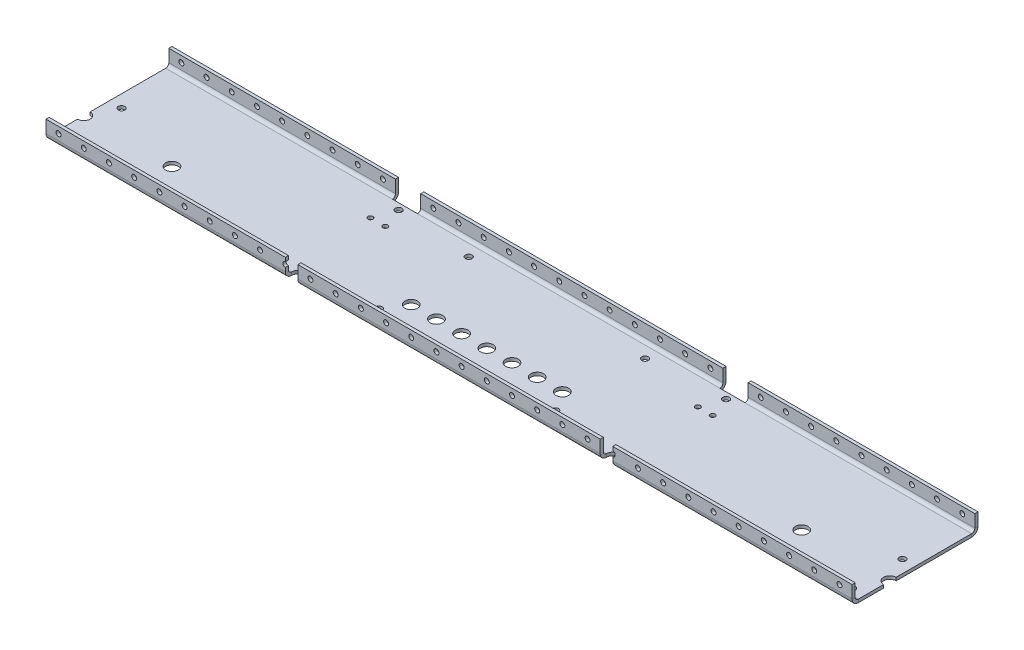
SolidWorks part; units mm, degrees
note: The reader was unsure of these and kept them because the rebuilt part matched: thickness of "Base-Flange1", "Edge-Flange1", "Sheet-Metal1", "Sheet-Metal2", "Sheet-Metal9", "Sheet-Metal10", "Sheet-Metal11", "Sheet-Metal12", "Sheet-Metal13", "Sheet-Metal14", "Sheet-Metal15", "Sheet-Metal16", "Sheet-Metal17", "Sheet-Metal18"; flange length of "Edge-Flange1".
ref_plane "Front Plane" through (0, 0, 0) normal (0, 0, 1) x (1, 0, 0)
ref_plane "Top Plane" through (0, 0, 0) normal (0, 1, 0) x (1, 0, 0)
ref_plane "Right Plane" through (0, 0, 0) normal (1, 0, 0) x (0, 0, -1)
sketch "Sketch1" plane through (0, 0, 0) normal (0, 1, 0) x (1, 0, 0)
  line L1 (406.4, -63.5) -> (-406.4, -63.5)
  line L2 (406.4, -63.5) -> (406.4, 63.5)
  line L3 (406.4, 63.5) -> (-406.4, 63.5)
  line L4 (-406.4, -63.5) -> (-406.4, 63.5)
  line L5 (406.4, -63.5) -> (-406.4, 63.5) construction
  line L6 (406.4, 63.5) -> (-406.4, -63.5) construction
  point P0 (0, 0)
  dimension "D1" = 127
  dimension "D2" = 812.8
base flange "Base-Flange1" sketch "Sketch1" thickness 3.175 reverse thickness direction no parameters "D1"=1
edge flange "Edge-Flange1" sketch "Sketch23" flange profiles "Sketch23", "Sketch25" flange angle 90 flange length 19.05 flange position material inside bend radius 3.175 thickness 3.175 relief rectangular parameters "D6"=10, "D8"=1
bend "EdgeBend1" bend radius 3.175 bend angle 90 parameters "D5"=1
bend "EdgeBend2" bend radius 3.175 bend angle 90 parameters "D5"=2
sketch "Sketch23" plane through (0, 0, -63.5) normal (0, 0, -1) x (-1, 0, 0)
  line L0 (-406.4, 0) -> (406.4, 0) construction
  line L1 (-406.4, 0) -> (406.4, 0)
  line L2 (-406.4, 0) -> (-406.4, 15.875)
  line L3 (-406.4, 15.875) -> (406.4, 15.875)
  line L4 (406.4, 15.875) -> (406.4, 0)
sketch "Sketch25" plane through (0, 0, 63.5) normal (0, 0, 1) x (1, 0, 0)
  line L0 (-406.4, 0) -> (406.4, 0) construction
  line L1 (-406.4, 0) -> (406.4, 0)
  line L2 (-406.4, 0) -> (-406.4, 15.875)
  line L3 (-406.4, 15.875) -> (406.4, 15.875)
  line L4 (406.4, 15.875) -> (406.4, 0)
hole_wizard "Mounting Holes" positions "Sketch19" profile "Sketch20" hole size "Ø5.0" standard "ANSI Metric" end condition through all
sketch "Sketch19" plane through (342.9, 0, -63.5) normal (0, 0, 1) x (1, 0, 0)
  line L0 (63.5, 9.525) -> (-749.3, 9.525) construction
  line L3 (63.5, 15.875) -> (63.5, 3.175) construction
  point P9 (-736.6, 9.525)
  dimension "D1" = 12.7
sketch "Sketch20" plane through (-393.7, 9.525, -63.5) normal (1, 0, 0) x (0, 1, 0)
  line L0 (0, 0) -> (0, 228.6)
  line L1 (0, 228.6) -> (2.5, 228.6)
  line L2 (2.5, 228.6) -> (2.5, 0)
  line L5 (2.5, 0) -> (0, 0)
  line L11 (0, -6.35) -> (0, 107.95) construction
  dimension "Thru Hole Dia." = 5
  dimension "Thru Hole Depth" = 228.6
pattern_linear "LPattern3" count 32 spacing 25.4 along (1, 0, 0) of "Mounting Holes"
sketch "Sketch21" plane through (0, -3.175, 0) normal (0, -1, 0) x (1, 0, 0)
  line L0 (406.4, 0) -> (177.8, 0) construction
  line L3 (177.8, -57.15) -> (152.4, -57.15)
  line L4 (177.8, -57.15) -> (177.8, -63.5)
  line L5 (177.8, -63.5) -> (152.4, -63.5)
  line L6 (152.4, -57.15) -> (152.4, -63.5)
  line L7 (-177.8, 0) -> (-406.4, 0) construction
  line L8 (-152.4, -63.5) -> (-177.8, -63.5)
  line L9 (-152.4, -63.5) -> (-152.4, -57.15)
  line L10 (-152.4, -57.15) -> (-177.8, -57.15)
  line L11 (-177.8, -63.5) -> (-177.8, -57.15)
  line L12 (-406.4, -57.15) -> (-406.4, 57.15) construction
  line L13 (406.4, 57.15) -> (406.4, -57.15) construction
  line L14 (-406.4, -63.5) -> (406.4, -63.5) construction
  line L15 (-406.4, -57.15) -> (406.4, -57.15) construction
  dimension "D1" = 228.6
  dimension "D3" = 25.4
extrude "Cut-Extrude3" cut sketch "Sketch21" against normal through all normal cut yes
sketch "Sketch26" plane through (0, 0, 0) normal (0, 1, 0) x (1, 0, 0)
  line L0 (406.4, -57.15) -> (-406.4, -57.15) construction
  line L1 (152.4, -57.15) -> (152.4, -63.5)
  line L2 (406.4, -63.5) -> (-406.4, -63.5) construction
  line L3 (152.4, -63.5) -> (165.1, -63.5)
  line L4 (165.1, -63.5) -> (165.1, -57.15)
  line L5 (-165.1, -57.15) -> (-165.1, -63.5)
  line L6 (-165.1, -63.5) -> (-152.4, -63.5)
  line L7 (-152.4, -63.5) -> (-152.4, -57.15)
  line L12 (0, 158.0045) -> (0, -158.0045) construction
  line L13 (152.4, -63.5) -> (-152.4, -63.5) construction
  arc A0 (-165.1, -57.15) -> (-152.4, -57.15) centre (-158.75, -57.15) cw
  arc A1 (152.4, -57.15) -> (165.1, -57.15) centre (158.75, -57.15) cw
  point P26 (0, 0)
  point P29 (0, -63.5)
  dimension "D2" = 6.35
  dimension "D1" = 304.8
extrude "Cut-Extrude4" cut sketch "Sketch26" against normal through all both and the other way through all
hole_wizard "80/20 Connection Holes" positions "Sketch27" profile "Sketch28" hole size "Ø6.0" standard "ANSI Metric" end condition through all
sketch "Sketch27" plane through (0, 0, 0) normal (0, 1, 0) x (1, 0, 0)
  line L0 (-152.4, 63.5) -> (152.4, 63.5) construction
  line L1 (-393.7, 0) -> (-393.7, -50.8) construction
  line L3 (393.7, -50.8) -> (393.7, 0) construction
  line L4 (406.4, -57.15) -> (406.4, 57.15) construction
  line L5 (393.7, -25.4) -> (406.4, -25.4) construction
  line L7 (-393.7, -25.4) -> (-406.4, -25.4) construction
  line L8 (-406.4, 57.15) -> (-406.4, -57.15) construction
  line L10 (393.7, -50.8) -> (393.7, -57.15) construction
  line L11 (406.4, -57.15) -> (165.1, -57.15) construction
  line L13 (-393.7, -50.8) -> (-393.7, -57.15) construction
  line L14 (-165.1, -57.15) -> (-406.4, -57.15) construction
  point P0 (-165.1, 50.8)
  point P2 (165.1, 50.8)
  point P10 (-393.7, 0)
  point P11 (-393.7, -50.8)
  point P14 (393.7, -50.8)
  point P15 (393.7, 0)
  dimension "D1" = 12.7
  dimension "D2" = 12.7
  dimension "D3" = 12.7
  dimension "D4" = 12.7
  dimension "D5" = 12.7
  dimension "D6" = 50.8
  dimension "D7" = 31.75
sketch "Sketch28" plane through (-165.1, 0, -50.8) normal (1, 0, 0) x (0, 0, 1)
  line L0 (0, 0) -> (0, 3.175)
  line L1 (0, 3.175) -> (3.3, 3.175)
  line L2 (3.3, 3.175) -> (3.3, 0)
  line L5 (3.3, 0) -> (0, 0)
  line L11 (0, -6.35) -> (0, 107.95) construction
  dimension "Thru Hole Dia." = 6.6
  dimension "Thru Hole Depth" = 3.175
hole_wizard "Motor Holes" positions "Sketch29" profile "Sketch30" hole size "1/2" standard "ANSI Inch" end condition through all
sketch "Sketch29" plane through (0, 0, 0) normal (0, 1, 0) x (1, 0, 0)
  line L0 (-165.1, -63.5) -> (-406.4, -63.5) construction
  line L1 (-317.5, -25.4) -> (317.5, -25.4) construction
  line L3 (0, 0) -> (0, -25.4) construction
  line L5 (-406.4, 57.15) -> (-406.4, -57.15) construction
  point P0 (-317.5, -25.4)
  point P2 (317.5, -25.4)
  dimension "D1" = 38.1
  dimension "D2" = 88.9
sketch "Sketch30" plane through (-317.5, 0, 25.4) normal (1, 0, 0) x (0, 0, 1)
  line L0 (0, 0) -> (0, 3.175)
  line L1 (0, 3.175) -> (6.35, 3.175)
  line L2 (6.35, 3.175) -> (6.35, 0)
  line L5 (6.35, 0) -> (0, 0)
  line L11 (0, -6.35) -> (0, 107.95) construction
  dimension "Thru Hole Dia." = 12.7
  dimension "Thru Hole Depth" = 3.175
hole_wizard "1/2 (0.5) Diameter Hole1" positions "Sketch31" profile "Sketch32" hole size "1/2" standard "ANSI Inch" end condition through all
sketch "Sketch31" plane through (0, 0, 0) normal (0, 1, 0) x (1, 0, 0)
  line L0 (0, 0) -> (0, -25.4) construction
  line L2 (0, -25.4) -> (-25.4, -25.4) construction
  line L3 (-25.4, -25.4) -> (-50.8, -25.4) construction
  line L4 (-50.8, -25.4) -> (-76.2, -25.4) construction
  line L6 (0, -25.4) -> (25.4, -25.4) construction
  line L7 (25.4, -25.4) -> (50.8, -25.4) construction
  line L8 (50.8, -25.4) -> (76.2, -25.4) construction
  line L9 (152.4, -63.5) -> (-152.4, -63.5) construction
  point P2 (0, -25.4)
  point P8 (-25.4, -25.4)
  point P10 (-50.8, -25.4)
  point P12 (-76.2, -25.4)
  point P17 (25.4, -25.4)
  point P19 (50.8, -25.4)
  point P21 (76.2, -25.4)
  dimension "D1" = 25.4
  dimension "D2" = 38.1
sketch "Sketch32" plane through (76.2, 0, 25.4) normal (1, 0, 0) x (0, 0, 1)
  line L0 (0, 0) -> (0, 3.175)
  line L1 (0, 3.175) -> (6.35, 3.175)
  line L2 (6.35, 3.175) -> (6.35, 0)
  line L5 (6.35, 0) -> (0, 0)
  line L11 (0, -6.35) -> (0, 107.95) construction
  dimension "Thru Hole Dia." = 12.7
  dimension "Thru Hole Depth" = 3.175
sketch "Sketch33" plane through (0, 0, 0) normal (0, 1, 0) x (1, 0, 0)
  line L0 (-406.4, -63.5) -> (-406.4, -25.4) construction
  line L1 (-406.4, 57.15) -> (-406.4, -57.15) construction
  line L2 (-406.4, -19.05) -> (-406.4, -31.75)
  line L3 (406.4, -63.5) -> (406.4, -25.4) construction
  line L4 (406.4, -57.15) -> (406.4, 57.15) construction
  line L5 (406.4, -19.05) -> (406.4, -31.75)
  arc A0 (-406.4, -19.05) -> (-406.4, -31.75) centre (-406.4, -25.4) cw
  arc A1 (406.4, -19.05) -> (406.4, -31.75) centre (406.4, -25.4) ccw
  dimension "D1" = 6.35
  dimension "D2" = 38.1
extrude "Cut-Extrude5" cut sketch "Sketch33" against normal through all
hole_wizard "Ø1.0mm Dowel Hole1" positions "Sketch34" profile "Sketch35" hole size "Ø1.0" standard "ANSI Metric" end condition through all
sketch "Sketch34" plane through (0, 0, 0) normal (0, 1, 0) x (1, 0, 0)
  line L0 (-165.1, 50.8) -> (-88.9, 50.8) construction
  line L1 (-88.9, 50.8) -> (-88.9, -63.5) construction
  line L3 (152.4, -63.5) -> (-152.4, -63.5) construction
  line L4 (165.1, 50.8) -> (88.9, 50.8) construction
  line L5 (88.9, 50.8) -> (88.9, -63.5) construction
  line L6 (-88.9, 45.28) -> (88.9, 45.28) construction
  line L8 (-88.9, -45.28) -> (88.9, -45.28) construction
  line L9 (-152.4, 63.5) -> (152.4, 63.5) construction
  point P16 (-88.9, 45.28)
  point P18 (-88.9, -45.28)
  point P22 (88.9, 45.28)
  point P25 (88.9, -45.28)
  dimension "D1" = 76.2
  dimension "D2" = 18.22
  dimension "D3" = 18.22
sketch "Sketch35" plane through (88.9, 0, 45.28) normal (1, 0, 0) x (0, 0, 1)
  line L0 (0, 0) -> (0, 3.175)
  line L1 (0, 3.175) -> (3.3, 3.175)
  line L2 (3.3, 3.175) -> (3.3, 0)
  line L5 (3.3, 0) -> (0, 0)
  line L11 (0, -6.35) -> (0, 107.95) construction
  dimension "Thru Hole Dia." = 6.6
  dimension "Thru Hole Depth" = 3.175
hole_wizard "Ø5.0mm Dowel Hole1" positions "Sketch40" profile "Sketch39" hole size "Ø5.0" standard "ANSI Metric" end condition through all
sketch "Sketch40" plane through (0, 0, 0) normal (0, 1, 0) x (1, 0, 0)
  line L0 (-165.1, 50.8) -> (-165.1, 29.8) construction
  line L2 (-172.6, 29.8) -> (-157.6, 29.8) construction
  line L4 (157.6, 29.8) -> (172.6, 29.8) construction
  line L5 (165.1, 29.8) -> (165.1, 50.8) construction
  point P6 (-172.6, 29.8)
  point P7 (-157.6, 29.8)
  point P10 (-165.1, 29.8)
  point P11 (157.6, 29.8)
  point P12 (172.6, 29.8)
  dimension "D1" = 15
  dimension "D2" = 21
sketch "Sketch39" plane through (172.6, 0, -29.8) normal (1, 0, 0) x (0, 0, 1)
  line L0 (0, 0) -> (0, 3.175)
  line L1 (0, 3.175) -> (2.5, 3.175)
  line L2 (2.5, 3.175) -> (2.5, 0)
  line L5 (2.5, 0) -> (0, 0)
  line L11 (0, -6.35) -> (0, 107.95) construction
  dimension "Thru Hole Dia." = 5
  dimension "Thru Hole Depth" = 3.175
sketch "Bend-Lines1" [suppressed] plane through (0, 0, 0) normal (0, 1, 0) x (1, 0, 0)
sketch "Bounding-Box1" [suppressed] plane through (0, 0, 0) normal (0, 1, 0) x (1, 0, 0)
sheet metal parameters "Sheet-Metal1" thickness 3.175 parameters "D1"=1, "D7"=3
flat pattern "Flat-Pattern1" [suppressed]
sketch "Bend-Lines2" plane through (0, 0, 0) normal (0, 1, 0) x (1, 0, 0)
sketch3d "Bounding-Box2" [suppressed]
  line L0 (-77.3309, 406.4, 0) -> (-77.3309, -406.4, 0) construction
  line L1 (77.3309, 406.4, 0) -> (77.3309, -406.4, 0) construction
  line L2 (-77.3309, 406.4, 0) -> (77.3309, 406.4, 0) construction
  line L3 (-77.3309, -406.4, 0) -> (77.3309, -406.4, 0) construction
sheet metal parameters "Sheet-Metal2" thickness 3.175 parameters "D1"=1, "D7"=3
flat pattern "Flat-Pattern1"
sketch "Bend-Lines2" plane through (0, 0, 0) normal (0, 1, 0) x (1, 0, 0)
  line L4 (-406.4, -60.8905) -> (406.4, -60.8905) construction
  line L5 (406.4, 60.8905) -> (-406.4, 60.8905) construction
  line L6 (-406.4, -60.8905) -> (406.4, -60.8905) construction
  line L7 (406.4, 60.8905) -> (-406.4, 60.8905) construction
  point P0 (-60.8905, 406.4)
  point P1 (-60.8905, -406.4)
  point P2 (60.8905, -406.4)
  point P3 (60.8905, 406.4)
sketch3d "Bounding-Box2" [suppressed]
  line L0 (406.4, -77.3309, 0) -> (-406.4, -77.3309, 0) construction
  line L1 (406.4, 77.3309, 0) -> (-406.4, 77.3309, 0) construction
  line L2 (406.4, -77.3309, 0) -> (406.4, 77.3309, 0) construction
  line L3 (-406.4, -77.3309, 0) -> (-406.4, 77.3309, 0) construction
bend of the flat pattern "Flatten-<EdgeBend1>1"
bend of the flat pattern "Flatten-<EdgeBend2>1"
sheet metal parameters "Sheet-Metal9" thickness 3.175 parameters "D1"=1, "D7"=3
flat pattern "Flat-Pattern1" [suppressed]
sketch "Bend-Lines2" plane through (0, 0, 0) normal (0, 1, 0) x (1, 0, 0)
  line L0 (-60.8905, 406.4) -> (-60.8905, -406.4) construction
  line L1 (60.8905, -406.4) -> (60.8905, 406.4) construction
  line L2 (-60.8905, 406.4) -> (-60.8905, -406.4) construction
  line L3 (60.8905, -406.4) -> (60.8905, 406.4) construction
sketch3d "Bounding-Box2" [suppressed]
  line L0 (-77.3309, 406.4, 0) -> (-77.3309, -406.4, 0) construction
  line L1 (77.3309, 406.4, 0) -> (77.3309, -406.4, 0) construction
  line L2 (-77.3309, 406.4, 0) -> (77.3309, 406.4, 0) construction
  line L3 (-77.3309, -406.4, 0) -> (77.3309, -406.4, 0) construction
bend of the flat pattern "Flatten-<EdgeBend2>2"
bend of the flat pattern "Flatten-<EdgeBend1>2"
sheet metal parameters "Sheet-Metal10" thickness 3.175 parameters "D1"=1, "D7"=3
flat pattern "Flat-Pattern1"
sketch "Bend-Lines2" plane through (0, 0, 0) normal (0, 1, 0) x (1, 0, 0)
  line L4 (-406.4, -60.8905) -> (406.4, -60.8905) construction
  line L5 (406.4, 60.8905) -> (-406.4, 60.8905) construction
  line L6 (-406.4, -60.8905) -> (406.4, -60.8905) construction
  line L7 (406.4, 60.8905) -> (-406.4, 60.8905) construction
sketch3d "Bounding-Box2" [suppressed]
  line L0 (406.4, -77.3309, 0) -> (-406.4, -77.3309, 0) construction
  line L1 (406.4, 77.3309, 0) -> (-406.4, 77.3309, 0) construction
  line L2 (406.4, -77.3309, 0) -> (406.4, 77.3309, 0) construction
  line L3 (-406.4, -77.3309, 0) -> (-406.4, 77.3309, 0) construction
bend of the flat pattern "Flatten-<EdgeBend2>3"
bend of the flat pattern "Flatten-<EdgeBend1>3"
sheet metal parameters "Sheet-Metal11" thickness 3.175 parameters "D1"=1, "D7"=3
flat pattern "Flat-Pattern1"
sketch "Bend-Lines2" plane through (0, 0, 0) normal (0, 1, 0) x (1, 0, 0)
  line L6 (-406.4, -60.8905) -> (406.4, -60.8905) construction
  line L7 (406.4, 60.8905) -> (-406.4, 60.8905) construction
  line L8 (-406.4, -60.8905) -> (406.4, -60.8905) construction
  line L9 (406.4, 60.8905) -> (177.8, 60.8905) construction
  line L10 (152.4, 60.8905) -> (-152.4, 60.8905) construction
  line L11 (-177.8, 60.8905) -> (-406.4, 60.8905) construction
  point P0 (-60.8905, 406.4)
  point P1 (-60.8905, -406.4)
  point P2 (60.8905, 177.8)
  point P3 (60.8905, 406.4)
sketch3d "Bounding-Box2" [suppressed]
  line L0 (406.4, -77.3309, 0) -> (-406.4, -77.3309, 0) construction
  line L1 (406.4, 77.3309, 0) -> (-406.4, 77.3309, 0) construction
  line L2 (406.4, -77.3309, 0) -> (406.4, 77.3309, 0) construction
  line L3 (-406.4, -77.3309, 0) -> (-406.4, 77.3309, 0) construction
bend of the flat pattern "Flatten-<EdgeBend2>4"
bend of the flat pattern "Flatten-<EdgeBend1>4"
sheet metal parameters "Sheet-Metal12" thickness 3.175 parameters "D1"=1, "D7"=3
flat pattern "Flat-Pattern1"
sketch "Bend-Lines2" plane through (0, 0, 0) normal (0, 1, 0) x (1, 0, 0)
  line L0 (-406.4, -60.8905) -> (-203.2, -60.8905) construction
  line L1 (-190.5, -60.8905) -> (190.5, -60.8905) construction
  line L6 (203.2, -60.8905) -> (406.4, -60.8905) construction
  line L7 (406.4, 60.8905) -> (-406.4, 60.8905) construction
  line L8 (203.2, -60.8905) -> (406.4, -60.8905) construction
  line L9 (406.4, 60.8905) -> (177.8, 60.8905) construction
  line L10 (152.4, 60.8905) -> (-152.4, 60.8905) construction
  line L11 (-177.8, 60.8905) -> (-406.4, 60.8905) construction
sketch3d "Bounding-Box2" [suppressed]
  line L0 (406.4, -77.3309, 0) -> (-406.4, -77.3309, 0) construction
  line L1 (406.4, 77.3309, 0) -> (-406.4, 77.3309, 0) construction
  line L2 (406.4, -77.3309, 0) -> (406.4, 77.3309, 0) construction
  line L3 (-406.4, -77.3309, 0) -> (-406.4, 77.3309, 0) construction
bend of the flat pattern "Flatten-<EdgeBend2>4"
bend of the flat pattern "Flatten-<EdgeBend1>4"
sheet metal parameters "Sheet-Metal13" thickness 3.175 parameters "D1"=1, "D7"=3
flat pattern "Flat-Pattern1"
sketch "Bend-Lines2" plane through (0, 0, 0) normal (0, 1, 0) x (1, 0, 0)
  line L0 (-406.4, -60.8905) -> (-203.2, -60.8905) construction
  line L1 (-190.5, -60.8905) -> (190.5, -60.8905) construction
  line L6 (203.2, -60.8905) -> (406.4, -60.8905) construction
  line L7 (406.4, 60.8905) -> (-406.4, 60.8905) construction
  line L8 (203.2, -60.8905) -> (406.4, -60.8905) construction
  line L9 (406.4, 60.8905) -> (177.8, 60.8905) construction
  line L10 (152.4, 60.8905) -> (-152.4, 60.8905) construction
  line L11 (-177.8, 60.8905) -> (-406.4, 60.8905) construction
sketch3d "Bounding-Box2" [suppressed]
  line L0 (406.4, -77.3309, 0) -> (-406.4, -77.3309, 0) construction
  line L1 (406.4, 77.3309, 0) -> (-406.4, 77.3309, 0) construction
  line L2 (406.4, -77.3309, 0) -> (406.4, 77.3309, 0) construction
  line L3 (-406.4, -77.3309, 0) -> (-406.4, 77.3309, 0) construction
bend of the flat pattern "Flatten-<EdgeBend2>4"
bend of the flat pattern "Flatten-<EdgeBend1>4"
sheet metal parameters "Sheet-Metal14" thickness 3.175 parameters "D1"=1, "D7"=3
flat pattern "Flat-Pattern1"
sketch "Bend-Lines2" plane through (0, 0, 0) normal (0, 1, 0) x (1, 0, 0)
  line L0 (-406.4, -60.8905) -> (-203.2, -60.8905) construction
  line L1 (-190.5, -60.8905) -> (190.5, -60.8905) construction
  line L6 (203.2, -60.8905) -> (406.4, -60.8905) construction
  line L7 (406.4, 60.8905) -> (-406.4, 60.8905) construction
  line L8 (203.2, -60.8905) -> (406.4, -60.8905) construction
  line L9 (406.4, 60.8905) -> (177.8, 60.8905) construction
  line L10 (152.4, 60.8905) -> (-152.4, 60.8905) construction
  line L11 (-177.8, 60.8905) -> (-406.4, 60.8905) construction
sketch3d "Bounding-Box2" [suppressed]
  line L0 (406.4, -77.3309, 0) -> (-406.4, -77.3309, 0) construction
  line L1 (406.4, 77.3309, 0) -> (-406.4, 77.3309, 0) construction
  line L2 (406.4, -77.3309, 0) -> (406.4, 77.3309, 0) construction
  line L3 (-406.4, -77.3309, 0) -> (-406.4, 77.3309, 0) construction
bend of the flat pattern "Flatten-<EdgeBend2>4"
bend of the flat pattern "Flatten-<EdgeBend1>4"
sheet metal parameters "Sheet-Metal15" thickness 3.175 parameters "D1"=1, "D7"=3
flat pattern "Flat-Pattern1"
sketch "Bend-Lines2" plane through (0, 0, 0) normal (0, 1, 0) x (1, 0, 0)
  line L0 (-406.4, -60.8905) -> (-203.2, -60.8905) construction
  line L1 (-190.5, -60.8905) -> (190.5, -60.8905) construction
  line L6 (203.2, -60.8905) -> (406.4, -60.8905) construction
  line L7 (406.4, 60.8905) -> (-406.4, 60.8905) construction
  line L8 (203.2, -60.8905) -> (406.4, -60.8905) construction
  line L9 (406.4, 60.8905) -> (177.8, 60.8905) construction
  line L10 (152.4, 60.8905) -> (-152.4, 60.8905) construction
  line L11 (-177.8, 60.8905) -> (-406.4, 60.8905) construction
sketch3d "Bounding-Box2" [suppressed]
  line L0 (406.4, -77.3309, 0) -> (-406.4, -77.3309, 0) construction
  line L1 (406.4, 77.3309, 0) -> (-406.4, 77.3309, 0) construction
  line L2 (406.4, -77.3309, 0) -> (406.4, 77.3309, 0) construction
  line L3 (-406.4, -77.3309, 0) -> (-406.4, 77.3309, 0) construction
bend of the flat pattern "Flatten-<EdgeBend2>4"
bend of the flat pattern "Flatten-<EdgeBend1>4"
sheet metal parameters "Sheet-Metal16" thickness 3.175 parameters "D1"=1, "D7"=3
flat pattern "Flat-Pattern1"
sketch "Bend-Lines2" plane through (0, 0, 0) normal (0, 1, 0) x (1, 0, 0)
  line L0 (-190.5, -60.8905) -> (190.5, -60.8905) construction
  line L1 (203.2, -60.8905) -> (406.4, -60.8905) construction
  line L6 (-406.4, -60.8905) -> (-203.2, -60.8905) construction
  line L7 (406.4, 60.8905) -> (-406.4, 60.8905) construction
  line L8 (-406.4, -60.8905) -> (-203.2, -60.8905) construction
  line L9 (406.4, 60.8905) -> (177.8, 60.8905) construction
  line L10 (152.4, 60.8905) -> (-152.4, 60.8905) construction
  line L11 (-177.8, 60.8905) -> (-406.4, 60.8905) construction
sketch3d "Bounding-Box2" [suppressed]
  line L0 (406.4, -77.3309, 0) -> (-406.4, -77.3309, 0) construction
  line L1 (406.4, 77.3309, 0) -> (-406.4, 77.3309, 0) construction
  line L2 (406.4, -77.3309, 0) -> (406.4, 77.3309, 0) construction
  line L3 (-406.4, -77.3309, 0) -> (-406.4, 77.3309, 0) construction
bend of the flat pattern "Flatten-<EdgeBend2>4"
bend of the flat pattern "Flatten-<EdgeBend1>4"
sheet metal parameters "Sheet-Metal17" thickness 3.175 parameters "D1"=1, "D7"=3
flat pattern "Flat-Pattern1"
sketch "Bend-Lines2" plane through (0, 0, 0) normal (0, 1, 0) x (1, 0, 0)
  line L0 (-190.5, -60.8905) -> (190.5, -60.8905) construction
  line L1 (203.2, -60.8905) -> (406.4, -60.8905) construction
  line L6 (-406.4, -60.8905) -> (-203.2, -60.8905) construction
  line L7 (406.4, 60.8905) -> (-406.4, 60.8905) construction
  line L8 (-406.4, -60.8905) -> (-203.2, -60.8905) construction
  line L9 (406.4, 60.8905) -> (177.8, 60.8905) construction
  line L10 (152.4, 60.8905) -> (-152.4, 60.8905) construction
  line L11 (-177.8, 60.8905) -> (-406.4, 60.8905) construction
sketch3d "Bounding-Box2" [suppressed]
  line L0 (406.4, -77.3309, 0) -> (-406.4, -77.3309, 0) construction
  line L1 (406.4, 77.3309, 0) -> (-406.4, 77.3309, 0) construction
  line L2 (406.4, -77.3309, 0) -> (406.4, 77.3309, 0) construction
  line L3 (-406.4, -77.3309, 0) -> (-406.4, 77.3309, 0) construction
bend of the flat pattern "Flatten-<EdgeBend2>4"
bend of the flat pattern "Flatten-<EdgeBend1>4"
sheet metal parameters "Sheet-Metal18" thickness 3.175 parameters "D1"=1, "D7"=3
flat pattern "Flat-Pattern1"
sketch "Bend-Lines2" plane through (0, 0, 0) normal (0, 1, 0) x (1, 0, 0)
  line L0 (-152.4, -60.8905) -> (152.4, -60.8905) construction
  line L1 (165.1, -60.8905) -> (406.4, -60.8905) construction
  line L6 (-406.4, -60.8905) -> (-165.1, -60.8905) construction
  line L7 (406.4, 60.8905) -> (-406.4, 60.8905) construction
  line L8 (-406.4, -60.8905) -> (-165.1, -60.8905) construction
  line L9 (406.4, 60.8905) -> (177.8, 60.8905) construction
  line L10 (152.4, 60.8905) -> (-152.4, 60.8905) construction
  line L11 (-177.8, 60.8905) -> (-406.4, 60.8905) construction
sketch3d "Bounding-Box2" [suppressed]
  line L0 (406.4, -77.3309, 0) -> (-406.4, -77.3309, 0) construction
  line L1 (406.4, 77.3309, 0) -> (-406.4, 77.3309, 0) construction
  line L2 (406.4, -77.3309, 0) -> (406.4, 77.3309, 0) construction
  line L3 (-406.4, -77.3309, 0) -> (-406.4, 77.3309, 0) construction
bend of the flat pattern "Flatten-<EdgeBend2>4"
bend of the flat pattern "Flatten-<EdgeBend1>4"
